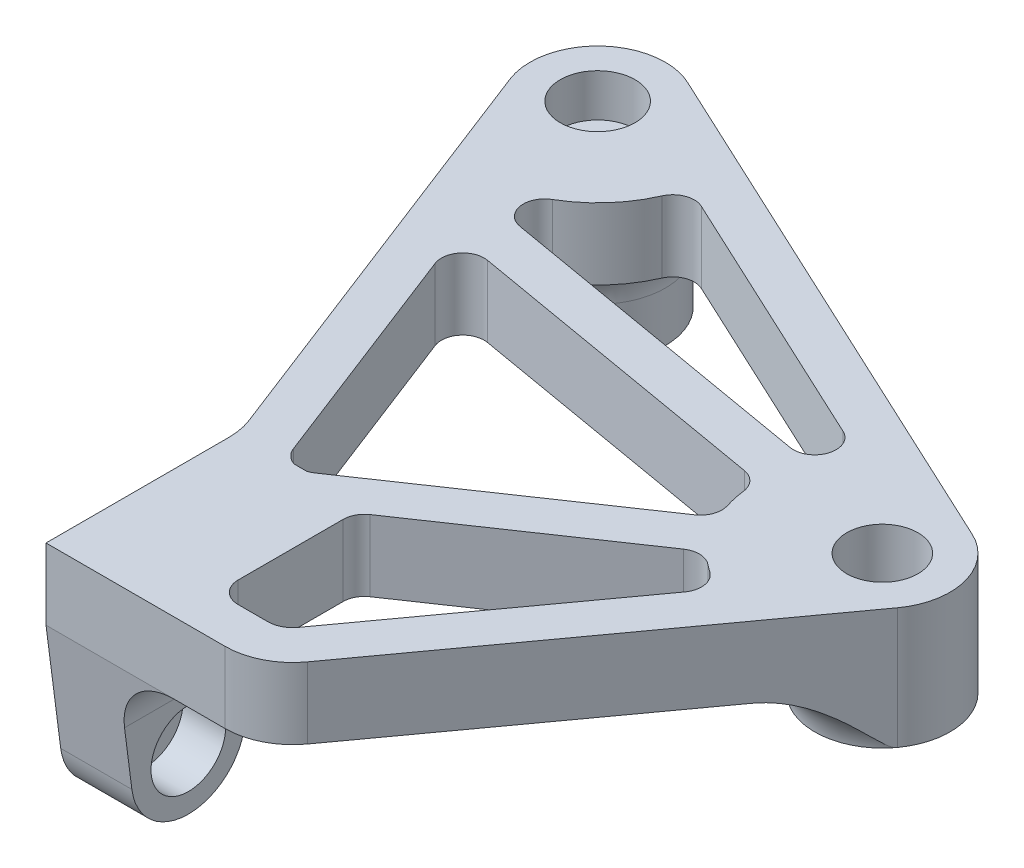
SolidWorks part; units mm, degrees
ref_plane "Front Plane" through (0, 0, 0) normal (0, 0, 1) x (1, 0, 0)
ref_plane "Top Plane" through (0, 0, 0) normal (0, 1, 0) x (1, 0, 0)
ref_plane "Right Plane" through (0, 0, 0) normal (1, 0, 0) x (0, 0, -1)
sketch "Sketch1" plane through (0, 0, 0) normal (0, 1, 0) x (1, 0, 0)
  line L0 (0, 0) -> (-60, 0) construction
  line L1 (-50, -57.5) -> (-30, -57.5)
  line L2 (-50, -32.5) -> (-60, -32.5)
  line L3 (-50, -32.5) -> (-50, -57.5)
  line L4 (-50, -57.5) -> (-60, -57.5)
  line L5 (-60, -32.5) -> (-60, -57.5)
  line L6 (-50, -32.5) -> (-60, -57.5) construction
  line L7 (-50, -57.5) -> (-60, -32.5) construction
  line L8 (-70.9826, 43.6087) -> (4.0174, 8.6087)
  line L9 (-60, -32.5) -> (-60, -30)
  line L10 (-30, -57.5) -> (7.688, -5.5807)
  line L11 (-60, -30) -> (-83.8582, 31.5673)
  circle A0 centre (0, 0) radius 5
  circle A1 centre (-75, 35) radius 3.1
  circle A2 centre (-75, 35) radius 9.5
  circle A3 centre (0, 0) radius 9.5
  point P8 (-55, -45)
  dimension "D1" = 10
  dimension "D3" = 19
  dimension "D11" = 6.2
  dimension "D2" = 35
  dimension "D4" = 60
  dimension "D5" = 25
  dimension "D6" = 10
  dimension "D7" = 80
  dimension "D8" = 15
  dimension "D9" = 20
  dimension "D10" = 2.5
extrude "Boss-Extrude1" add sketch "Sketch1" along normal blind 10
sketch "Sketch2" plane through (0, 0, 0) normal (0, -1, 0) x (1, 0, 0)
  circle A0 centre (-75, -35) radius 9.5
  circle A1 centre (-75, -35) radius 3.1 construction
  circle A2 centre (-75, -35) radius 3.1
  arc A3 (-83.8582, -31.5673) -> (-70.9826, -43.6087) centre (-75, -35) ccw construction
extrude "Boss-Extrude2" add sketch "Sketch2" along normal blind 15
sketch "Sketch3" plane through (-60, 0, 0) normal (1, 0, 0) x (0, 0, -1)
  line L0 (-47.5, 10) -> (-47.5, -15) construction
  line L1 (-57.5, 0) -> (-30, 0) construction
  line L2 (-57.5, 0) -> (-5.5807, 0) construction
  line L3 (-57.5, 0) -> (-55.4343, -16.0229)
  line L4 (-37.5, 0) -> (-39.5657, -16.0229)
  line L5 (-57.5, 10) -> (-5.5807, 10) construction
  line L6 (-57.5, 10) -> (-57.5, 0) construction
  circle A0 centre (-47.5, -15) radius 8
  circle A1 centre (-47.5, -15) radius 3.1
  point P5 (-47.5, -23)
  dimension "D1" = 16
  dimension "D3" = 6.2
  dimension "D2" = 10
  dimension "D4" = 15
extrude "Boss-Extrude3" add sketch "Sketch3" along normal blind 10
sketch "Sketch5" plane through (-50, 0, 0) normal (1, 0, 0) x (0, 0, -1)
  circle A0 centre (-47.5, -15) radius 5.25
  circle A2 centre (-47.5, -15) radius 3.1 construction
  dimension "D1" = 10.5
extrude "Cut-Extrude2" cut sketch "Sketch5" against normal blind 6
sketch "Sketch6" plane through (0, 10, 0) normal (0, 1, 0) x (1, 0, 0)
  line L0 (-75, 35) -> (0, 0) construction
  circle A2 centre (-75, 35) radius 5.25
  dimension "D2" = 10.5
extrude "Cut-Extrude3" cut sketch "Sketch6" against normal blind 6
sketch "Sketch9" plane through (0, 0, 0) normal (0, -1, 0) x (1, 0, 0)
  circle A0 centre (0, 0) radius 9.5
  arc A1 (4.0174, -8.6087) -> (7.688, 5.5807) centre (0, 0) ccw construction
  circle A2 centre (0, 0) radius 5 construction
  circle A3 centre (0, 0) radius 5
extrude "Boss-Extrude5" add sketch "Sketch9" along normal blind 7
fillet "Fillet6" radius 9.5 2 edges at (-60, 5, 30) (-30, 5, 57.5)
fillet "Fillet2" radius 8 4 edges at (-68.511, 0, -28.0615) (-50, 0, 47.5) (-55, 0, 37.5) (-9.1973, 0, 2.3792)
sketch "Sketch7" plane through (0, 0, 0) normal (0, -1, 0) x (1, 0, 0)
  line L0 (-36, 51.5) -> (-42, 51.5)
  line L1 (-42, 57.5) -> (-42, 30.4651) construction
  line L2 (-42, 51.5) -> (-42, 30.4651)
  line L3 (-42, 30.4651) -> (-53.385, 30.4651)
  line L4 (-42, 30.4651) -> (-60.0909, 30.4651) construction
  line L5 (-53.385, 30.4651) -> (-55.7101, 24.4651)
  line L9 (-36, 24.4651) -> (0, 0) construction
  line L13 (0, 0) -> (-69.8669, -12.0675) construction
  line L15 (-37.6862, 21.9839) -> (-7.8277, 1.6924)
  line L18 (-7.8277, 1.6924) -> (-70.3775, -9.1112)
  line L19 (-34.3138, 26.9464) -> (7.8277, -1.6924)
  line L20 (7.8277, -1.6924) -> (-69.3563, -15.0237)
  line L21 (-10.7812, 20.8103) -> (-32.0106, 50.0561)
  line L22 (-34.843, 51.5) -> (-36, 51.5)
  line L23 (-36, 51.5) -> (-36, 24.4651)
  line L28 (-55.7101, 24.4651) -> (-69.8669, -12.0675)
  line L37 (-52.4621, -28.3447) -> (-19.5202, -12.9718)
  line L39 (-10.7812, 20.8103) -> (-32.0106, 50.0561)
  line L40 (-34.843, 51.5) -> (-36, 51.5)
  line L43 (-55.7101, 24.4651) -> (-69.8669, -12.0675)
  line L44 (-52.4621, -28.3447) -> (-19.5202, -12.9718)
  line L45 (-37.6862, 21.9839) -> (-50.1662, 30.4651)
  line L46 (-34.3138, 26.9464) -> (-42, 32.1699)
  line L51 (-69.8669, -12.0675) -> (-72.068, -17.7474)
  line L52 (-36, 51.5) -> (-36, 24.4651)
  line L54 (-36, 24.4651) -> (-55.7101, 24.4651)
  line L55 (-36, 24.4651) -> (-55.7101, 24.4651)
  line L56 (-52.4621, -28.3447) -> (-57.9821, -30.9207)
  line L57 (-10.7812, 20.8103) -> (-7.2025, 15.8802)
  line L58 (-19.5202, -12.9718) -> (-13.9997, -10.3955)
  line L59 (-69.3563, -15.0237) -> (-71.1313, -15.3303)
  arc A2 (-57.6645, -37.3936) -> (-78.5477, -17.8634) centre (-75, -35) ccw construction
  arc A4 (-57.6645, -37.3936) -> (-78.5477, -17.8634) centre (-75, -35) ccw
  arc A10 (-0.9017, 17.4139) -> (-9.233, -14.7922) centre (0, 0) ccw construction
  circle A12 centre (0, 0) radius 9.5
  arc A13 (4.0174, -8.6087) -> (7.688, 5.5807) centre (0, 0) ccw construction
  arc A27 (-32.0106, 50.0561) -> (-34.843, 51.5) centre (-34.843, 48) ccw
  arc A28 (-52.4621, -28.3447) -> (-69.8669, -12.0675) centre (-75, -35) ccw
  arc A30 (-32.0106, 50.0561) -> (-34.843, 51.5) centre (-34.843, 48) ccw
  arc A33 (-0.9017, 17.4139) -> (-9.233, -14.7922) centre (0, 0) ccw
  circle A38 centre (-51.2799, 27.5948) radius 3
  arc A40 (-52.4621, -28.3447) -> (-69.8669, -12.0675) centre (-75, -35) ccw
  arc A42 (-10.7812, 20.8103) -> (-19.5202, -12.9718) centre (0, 0) ccw
  arc A43 (-10.7812, 20.8103) -> (-19.5202, -12.9718) centre (0, 0) ccw
  circle A44 centre (-63.89, -4.9463) radius 3
  circle A46 centre (-64.7154, -17.2665) radius 3
  circle A47 centre (-18.837, -9.3424) radius 3
  dimension "D4" = 6
  dimension "D1" = 6
  dimension "D2" = 3
  dimension "D3" = 3
extrude "Cut-Extrude4" cut sketch "Sketch7" against normal up to next
fillet "Fillet7" radius 3 7 edges at (-57.9821, 5, -30.9207) (-15.8933, 5, 7.1737) (-17.4372, 5, 0.0327) (-7.2025, 5, 15.8802) (-12.5208, 5, 12.1362) (-42, 5, 32.1699) (-42, 5, 51.5)
